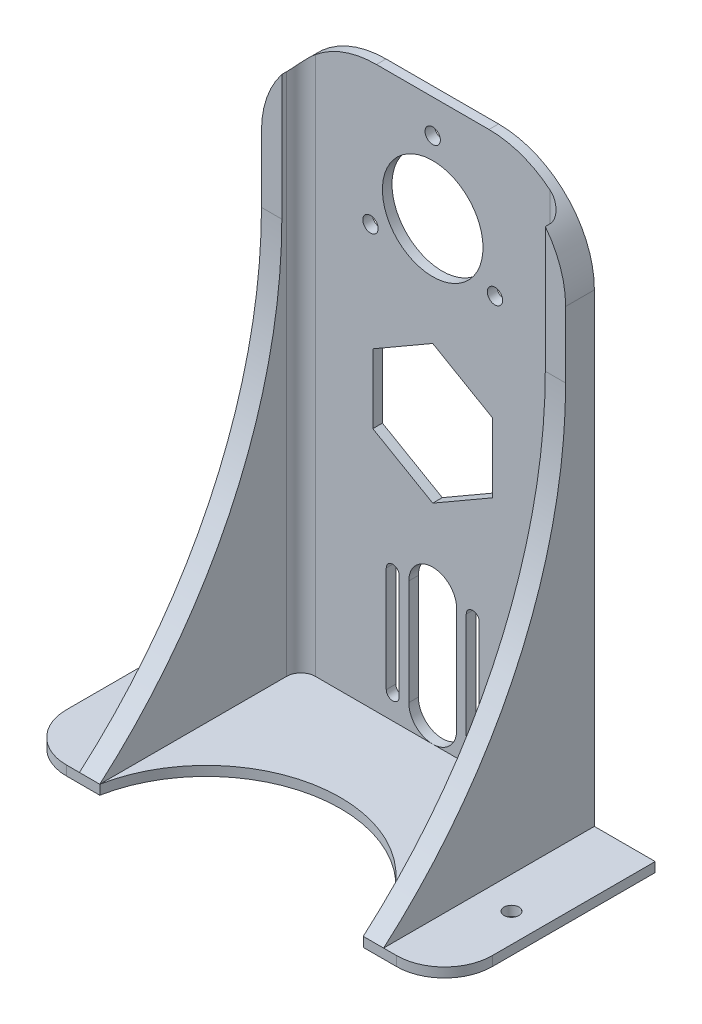
SolidWorks part; units mm, degrees
ref_plane "Front Plane" through (0, 0, 0) normal (0, 0, 1) x (1, 0, 0)
ref_plane "Top Plane" through (0, 0, 0) normal (0, 1, 0) x (1, 0, 0)
ref_plane "Right Plane" through (0, 0, 0) normal (1, 0, 0) x (0, 0, -1)
sketch "Sketch1" plane through (0, 0, 0) normal (0, 1, 0) x (1, 0, 0)
  line L1 (44.45, -45) -> (-44.45, -45)
  line L2 (44.45, -45) -> (44.45, 45)
  line L3 (44.45, 45) -> (-44.45, 45)
  line L4 (-44.45, -45) -> (-44.45, 45)
  line L5 (44.45, -45) -> (-44.45, 45) construction
  line L6 (44.45, 45) -> (-44.45, -45) construction
  point P0 (0, 0)
  dimension "D1" = 90
  dimension "D2" = 88.9
extrude "Base" add sketch "Sketch1" along normal blind 2
sketch "Sketch2" plane through (0, 2, 0) normal (0, 1, 0) x (1, 0, 0)
  line L0 (-44.45, 45) -> (-44.45, -45) construction
  line L1 (31.75, -1) -> (-31.75, -1)
  line L2 (31.75, -1) -> (31.75, -7)
  line L3 (31.75, -7) -> (-31.75, -7)
  line L4 (-31.75, -1) -> (-31.75, -7)
  line L5 (31.75, -1) -> (-31.75, -7) construction
  line L6 (31.75, -7) -> (-31.75, -1) construction
  line L7 (44.45, -45) -> (44.45, 45) construction
  line L8 (-44.45, -45) -> (44.45, -45) construction
  point P0 (0, -4)
  dimension "D1" = 6
  dimension "D2" = 63.5
  dimension "D3" = 12.7
  dimension "D4" = 12.7
  dimension "D5" = 38
extrude "Face Plate" add sketch "Sketch2" along normal blind 117
sketch "Sketch5" plane through (0, 0, 7) normal (0, 0, 1) x (1, 0, 0)
  line L0 (31.75, 119) -> (31.75, 2) construction
  line L1 (-8.35, 7) -> (-8.35, 29) construction
  line L2 (0, 112) -> (0, 97) construction
  line L3 (-31.75, 2) -> (31.75, 2) construction
  line L4 (-9.7, 7) -> (-9.7, 29)
  line L5 (-7, 7) -> (-7, 29)
  line L6 (8.35, 29) -> (8.35, 7) construction
  line L7 (9.7, 29) -> (9.7, 7)
  line L8 (7, 29) -> (7, 7)
  line L9 (0, 97) -> (12.9904, 89.5) construction
  line L10 (0, 119) -> (0, 2) construction
  line L11 (0, 97) -> (-12.9904, 89.5) construction
  line L12 (0, 7) -> (0, 29) construction
  line L15 (-44.45, 2) -> (44.45, 2) construction
  line L17 (-31.75, 119) -> (31.75, 119) construction
  line L18 (-5, 7) -> (-5, 29)
  line L19 (5, 7) -> (5, 29)
  circle A0 centre (0, 97) radius 10.5
  arc A1 (-5, 7) -> (5, 7) centre (0, 7) ccw
  arc A2 (5, 29) -> (-5, 29) centre (0, 29) ccw
  arc A3 (-9.7, 7) -> (-7, 7) centre (-8.35, 7) ccw
  arc A4 (-7, 29) -> (-9.7, 29) centre (-8.35, 29) ccw
  arc A5 (9.7, 29) -> (7, 29) centre (8.35, 29) ccw
  arc A6 (7, 7) -> (9.7, 7) centre (8.35, 7) ccw
  circle A7 centre (0, 97) radius 15 construction
  circle A8 centre (12.9904, 89.5) radius 1.6
  circle A9 centre (-12.9904, 89.5) radius 1.6
  circle A10 centre (0, 112) radius 1.6
  point P15 (-8.35, 18)
  point P20 (8.35, 18)
  point P36 (0, 18)
  dimension "D3" = 21
  dimension "D4" = 22
  dimension "D6" = 10
  dimension "D20" = 3.2
  dimension "D17" = 30
  dimension "D18" = 120
  dimension "D19" = 120
  dimension "D2" = 31.75
  dimension "D5" = 0
  dimension "D7" = 8.35
  dimension "D8" = 16
  dimension "D9" = 16
  dimension "D10" = 8.35
  dimension "D11" = 22
  dimension "D12" = 16
  dimension "D13" = 2.7
  dimension "D14" = 2.7
  dimension "D15" = 22
  dimension "D16" = 22
extrude "Face Holes" cut sketch "Sketch5" against normal through all
fillet "Fillet2" radius 10 4 edges at (-44.45, 1, 45) (-44.45, 1, -45) (44.45, 1, 45) (44.45, 1, -45)
sketch "Sketch23" plane through (0, 0, 7) normal (0, 0, 1) x (1, 0, 0)
  line L0 (-31.75, 2) -> (0, 2) construction
  line L2 (-27.5, 119) -> (-27.5, 2)
  line L3 (-27.5, 2) -> (27.5, 2)
  line L4 (27.5, 119) -> (27.5, 2)
  line L5 (31.75, 119) -> (-31.75, 119) construction
  line L6 (27.5, 119) -> (-27.5, 119)
  circle A1 centre (0, 97) radius 10.5 construction
  dimension "D2" = 55
  dimension "D3" = 27.5
fillet "Fillet3" radius 20 2 edges at (31.75, 119, 4) (-31.75, 119, 4)
extrude "Cut-Extrude6" cut sketch "Sketch23" against normal blind 4 contours L6 L2 L3 L4
fillet "Fillet4" radius 110 2 edges at (29.625, 2, 7) (-29.625, 2, 7)
sketch "Sketch24" plane through (0, 2, 0) normal (0, 1, 0) x (1, 0, 0)
  line L0 (44.45, -35) -> (44.45, 35) construction
  line L1 (44.45, -1) -> (-44.45, -1)
  line L2 (44.45, -1) -> (44.45, 45)
  line L3 (44.45, 45) -> (-44.45, 45)
  line L4 (-44.45, -1) -> (-44.45, 45)
extrude "Cut-Extrude7" cut sketch "Sketch24" against normal blind 3
sketch "Sketch25" plane through (0, 2, 0) normal (0, 1, 0) x (1, 0, 0)
  line L0 (-27.5, -45) -> (27.5, -45) construction
  line L1 (-44.45, -1) -> (-44.45, -35) construction
  line L2 (44.45, -35) -> (44.45, -1) construction
  circle A0 centre (38.45, -25) radius 1.55
  circle A1 centre (-38.45, -25) radius 1.55
  dimension "D1" = 3.1
  dimension "D2" = 20
  dimension "D3" = 6
  dimension "D4" = 6
  dimension "D5" = 20
  dimension "D6" = 3.1
extrude "Cut-Extrude8" cut sketch "Sketch25" against normal through all
sketch "Sketch26" plane through (0, 2, 0) normal (0, 1, 0) x (1, 0, 0)
  line L0 (-27.5, -45) -> (27.5, -45)
  arc A0 (-27.5, -45) -> (27.5, -45) centre (0, -50.2678) cw
  dimension "D1" = 28
extrude "Cut-Extrude9" cut sketch "Sketch26" against normal through all
fillet "Fillet5" radius 3 2 edges at (27.5, 56.6631, 3) (-27.5, 56.6631, 3)
sketch "Sketch27" plane through (0, 0, 3) normal (0, 0, 1) x (1, 0, 0)
  line L0 (-27.5, 0) -> (27.5, 0) construction
  line L1 (0, 45.5662) -> (12.5, 52.7831)
  line L2 (12.5, 52.7831) -> (12.5, 67.2169)
  line L3 (12.5, 67.2169) -> (0, 74.4338)
  line L4 (0, 74.4338) -> (-12.5, 67.2169)
  line L5 (-12.5, 67.2169) -> (-12.5, 52.7831)
  line L6 (-12.5, 52.7831) -> (0, 45.5662)
  circle A0 centre (0, 60) radius 12.5 construction
  dimension "D1" = 60
  dimension "D2" = 25
extrude "Cut-Extrude10" cut sketch "Sketch27" against normal through all
